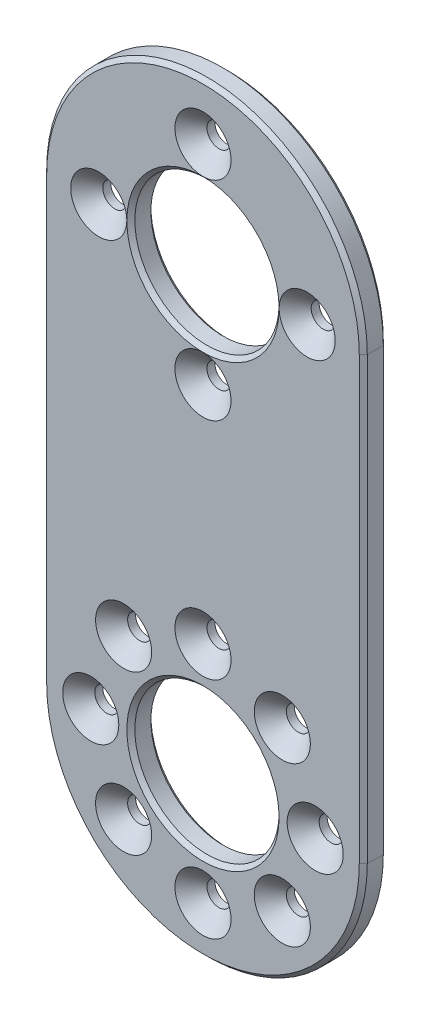
SolidWorks part; units mm, degrees
ref_plane "Face" through (0, 0, 0) normal (0, 0, 1) x (1, 0, 0)
ref_plane "Dessus" through (0, 0, 0) normal (0, 1, 0) x (1, 0, 0)
ref_plane "Droite" through (0, 0, 0) normal (1, 0, 0) x (0, 0, -1)
sketch "Esquisse1" plane through (0, 0, 0) normal (0, 0, 1) x (1, 0, 0)
  line L0 (0, 0) -> (0, 55)
  line L1 (40, 55) -> (40, 0)
  line L2 (20, 75) -> (20, -20) construction
  line L3 (0, 55) -> (40, 55) construction
  line L4 (0, 0) -> (40, 0) construction
  line L5 (20, -20) -> (40, -20) construction
  line L6 (40, -20) -> (20, 0) construction
  line L7 (20, 0) -> (0, 20) construction
  line L8 (40, 0) -> (40, -20) construction
  line L9 (20, -20) -> (0, -20) construction
  line L10 (0, -20) -> (0, 0) construction
  line L11 (0, -20) -> (20, 0) construction
  line L12 (20, 0) -> (40, 20) construction
  arc A0 (0, 55) -> (40, 55) centre (20, 55) cw
  arc A1 (0, 0) -> (40, 0) centre (20, 0) ccw
  circle A2 centre (20, 55) radius 9
  circle A3 centre (20, 0) radius 9
  circle A4 centre (20, 68) radius 1.5
  circle A5 centre (20, 42) radius 1.5
  circle A6 centre (7, 55) radius 1.5
  circle A7 centre (33, 55) radius 1.5
  circle A8 centre (10.1005, 9.8995) radius 1.5
  circle A9 centre (6, 0) radius 1.5
  circle A10 centre (10.1005, -9.8995) radius 1.5
  circle A11 centre (20, -14) radius 1.5
  circle A12 centre (29.8995, -9.8995) radius 1.5
  circle A13 centre (34, 0) radius 1.5
  circle A14 centre (29.8995, 9.8995) radius 1.5
  circle A15 centre (20, 14) radius 1.5
  point P24 (6, 0)
  point P25 (10.1005, 9.8995)
  point P26 (20, 14)
  point P27 (29.8995, 9.8995)
  point P28 (34, 0)
  point P29 (20, -14)
  point P30 (10.1005, -9.8995)
  point P31 (29.8995, -9.8995)
  dimension "D1" = 20
  dimension "D3" = 18
  dimension "D5" = 3
  dimension "D7" = 18
  dimension "D9" = 14
  dimension "D16" = 3
  dimension "D2" = 55
  dimension "D4" = 26
  dimension "D6" = 26
  dimension "D8" = 14
  dimension "D10" = 14
  dimension "D11" = 14
  dimension "D12" = 14
  dimension "D13" = 14
  dimension "D14" = 14
  dimension "D15" = 14
extrude "Extrusion1" add sketch "Esquisse1" along normal blind 3
chamfer "Chanfrein1" distance 2 angle 45 12 edges at (7.5, 0, 3) (11.6005, -9.8995, 3) (21.5, -14, 3) (31.3995, -9.8995, 3) (35.5, 0, 3) (31.3995, 9.8995, 3) (21.5, 14, 3) (11.6005, 9.8995, 3) (18.5, 42, 3) (31.5, 55, 3) (21.5, 68, 3) (8.5, 55, 3)
chamfer "Chanfrein2" distance 0.5 angle 45 12 edges at (29, 0, 0) (29, 0, 3) (29, 55, 3) (29, 55, 0) (0, 27.5, 0) (20, -20, 0) (40, 27.5, 0) (20, 75, 0) (20, 75, 3) (0, 27.5, 3) (20, -20, 3) (40, 27.5, 3)
